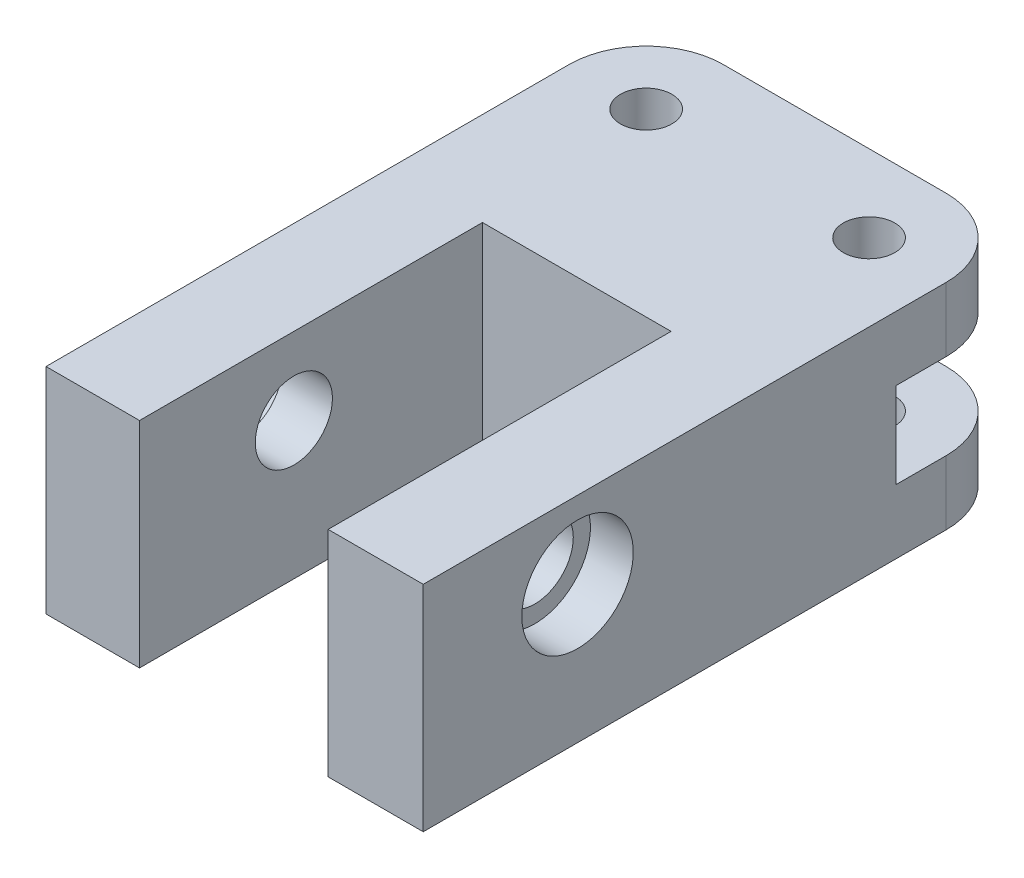
SolidWorks part; units mm, degrees
ref_plane "정면" through (0, 0, 0) normal (0, 0, 1) x (1, 0, 0)
ref_plane "윗면" through (0, 0, 0) normal (0, 1, 0) x (1, 0, 0)
ref_plane "우측면" through (0, 0, 0) normal (1, 0, 0) x (0, 0, -1)
sketch "스케치1" plane through (0, 0, 0) normal (0, 0, 1) x (1, 0, 0)
  line L1 (-22, -12.5) -> (22, -12.5)
  line L2 (-22, -12.5) -> (-22, 12.5)
  line L3 (-22, 12.5) -> (22, 12.5)
  line L4 (22, -12.5) -> (22, 12.5)
  line L5 (-22, -12.5) -> (22, 12.5) construction
  line L6 (-22, 12.5) -> (22, -12.5) construction
  point P0 (0, 0)
  dimension "D1" = 44
  dimension "D2" = 25
extrude "보스-돌출1" add sketch "스케치1" along normal blind 70
sketch "스케치2" plane through (0, 0, 70) normal (0, 0, 1) x (1, 0, 0)
  line L0 (-22, -12.5) -> (22, -12.5) construction
  line L1 (-11.0921, -12.5) -> (10.9079, -12.5)
  line L2 (-11.0921, -12.5) -> (-11.0921, 12.5)
  line L3 (-11.0921, 12.5) -> (10.9079, 12.5)
  line L4 (10.9079, -12.5) -> (10.9079, 12.5)
  line L5 (22, 12.5) -> (-22, 12.5) construction
  dimension "D1" = 22
extrude "컷-돌출1" cut sketch "스케치2" against normal blind 40
sketch "스케치3" plane through (22, 0, 0) normal (1, 0, 0) x (0, 0, -1)
  line L0 (-70, -12.5) -> (-70, 12.5) construction
  line L1 (-70, 0) -> (-16.1635, 0) construction
  line L2 (-30, -12.5) -> (-30, 12.5) construction
  line L3 (-30, -12.5) -> (-30, 12.5) construction
  line L4 (-70, 12.5) -> (0, 12.5) construction
  circle A0 centre (-52, 3.5) radius 4.5
  dimension "D1" = 9
  dimension "D2" = 22
  dimension "D3" = 9
extrude "컷-돌출2" cut sketch "스케치3" against normal blind 50
sketch "스케치4" plane through (22, 0, 0) normal (-1, 0, 0) x (0, 0, 1)
  circle A0 centre (52, 3.5) radius 6.5
  dimension "D1" = 13
extrude "컷-돌출4" cut sketch "스케치4" along normal blind 5 contours A0
sketch "스케치5" plane through (0, 12.5, 0) normal (0, 1, 0) x (1, 0, 0)
  line L0 (13, -9) -> (56.6647, -9) construction
  line L1 (13, -9) -> (13, 25.2953) construction
  line L2 (22, -70) -> (22, 0) construction
  line L3 (22, 0) -> (-22, 0) construction
  line L4 (13, 12.3557) -> (13, 0)
  line L5 (22, -9) -> (34.3557, -9)
  circle A0 centre (13, -9) radius 3
  arc A1 (22, -9) -> (13, 0) centre (13, -9) ccw
  arc A2 (34.3557, -9) -> (13, 12.3557) centre (13, -9) ccw
  dimension "D1" = 6
  dimension "D2" = 9
  dimension "D3" = 9
extrude "컷-돌출5" cut sketch "스케치5" against normal blind 29
mirror "대칭 복사2" about plane through (0, 0, 0) normal (1, 0, 0) of "컷-돌출5", "컷-돌출4"
ref_point "점1"
ref_point "점2"
ref_axis "기준축1" through (33.6861, 12.5, 9) along (-1, 0, 0)
sketch "스케치6" plane through (0, 0, 0) normal (0, 1, 0) x (1, 0, 0)
  line L0 (22, -70) -> (22, -9) construction
  line L2 (2.5, -19.5) -> (2.5, 5.2581)
  line L3 (22, -14.8492) -> (22, 5.2581)
  line L4 (22, 5.2581) -> (2.5, 5.2581)
  line L7 (17.3492, -19.5) -> (2.5, -19.5)
  line L9 (33.6861, -9) -> (-20.6842, -9) construction
  line L10 (17.3492, -19.5) -> (22, -14.8492)
  line L11 (13, -9) -> (2.5, -19.5) construction
  line L12 (-22, -14.8492) -> (-22, 5.2581)
  line L14 (0, -24.5) -> (0, 0) construction
  line L15 (-2.5, -19.5) -> (-2.5, 5.2581)
  line L16 (-17.3492, -19.5) -> (-2.5, -19.5)
  line L17 (-17.3492, -19.5) -> (-22, -14.8492)
  line L18 (-2.5, 5.2581) -> (-22, 5.2581)
  dimension "D1" = 10.5
  dimension "D2" = 10.5
  dimension "D3" = 45
  dimension "D4" = 10.5
extrude "컷-돌출6" cut sketch "스케치6" against normal blind 5 and the other way blind 5
